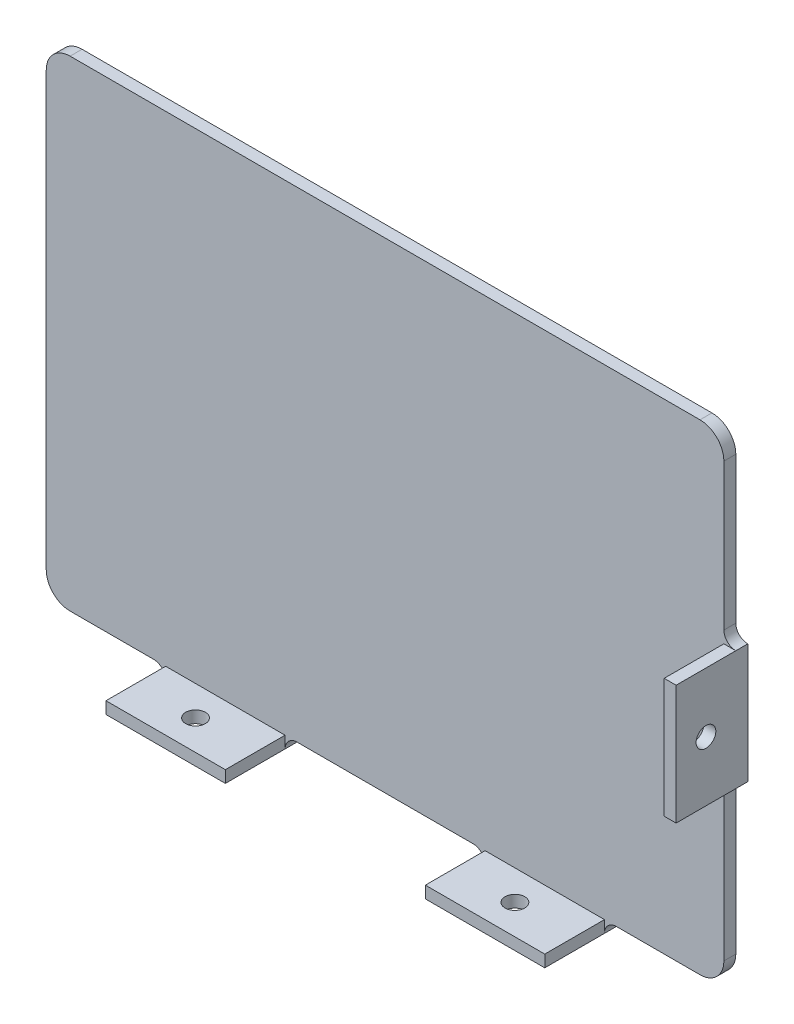
SolidWorks part; units mm, degrees
ref_plane "前视基准面" through (0, 0, 0) normal (0, 0, 1) x (1, 0, 0)
ref_plane "上视基准面" through (0, 0, 0) normal (0, 1, 0) x (1, 0, 0)
ref_plane "右视基准面" through (0, 0, 0) normal (1, 0, 0) x (0, 0, -1)
sketch "草图1" plane through (0, 0, 0) normal (0, 0, 1) x (1, 0, 0)
  line L1 (4, 0) -> (109.5, 0)
  line L2 (0, 4) -> (0, 76.5)
  line L3 (4, 80.5) -> (109.5, 80.5)
  line L4 (113.5, 4) -> (113.5, 76.5)
  arc A0 (4, 0) -> (0, 4) centre (4, 4) cw
  arc A1 (109.5, 0) -> (113.5, 4) centre (109.5, 4) ccw
  arc A2 (109.5, 80.5) -> (113.5, 76.5) centre (109.5, 76.5) cw
  arc A3 (0, 76.5) -> (4, 80.5) centre (4, 76.5) cw
  point P7 (0, 0)
  point P10 (113.5, 0)
  point P15 (0, 80.5)
  dimension "D3" = 4
  dimension "D1" = 113.5
  dimension "D2" = 80.5
extrude "凸台-拉伸1" add sketch "草图1" along normal blind 2
sketch "草图2" plane through (0, 0, 2) normal (0, 0, 1) x (1, 0, 0)
  line L0 (113.5, 4) -> (113.5, 76.5) construction
  line L1 (113.5, 50) -> (115.5, 50)
  line L2 (113.5, 50) -> (113.5, 30)
  line L3 (113.5, 30) -> (115.5, 30)
  line L4 (115.5, 50) -> (115.5, 30)
  line L5 (4, 0) -> (109.5, 0) construction
  line L10 (20, 0) -> (40, 0)
  line L11 (20, 0) -> (20, -2)
  line L12 (20, -2) -> (40, -2)
  line L13 (40, 0) -> (40, -2)
  line L14 (0, 76.5) -> (0, 4) construction
  line L15 (73.5, 0) -> (93.5, 0)
  line L16 (73.5, 0) -> (73.5, -2)
  line L17 (73.5, -2) -> (93.5, -2)
  line L18 (93.5, 0) -> (93.5, -2)
  point P6 (93.5, -3.0466)
  point P22 (93.5, -1)
  dimension "D1" = 20
  dimension "D2" = 20
  dimension "D3" = 2
  dimension "D4" = 2
  dimension "D5" = 20
  dimension "D7" = 20
  dimension "D8" = 20
  dimension "D9" = 30
extrude "凸台-拉伸2" add sketch "草图2" along normal blind 10 and the other way blind 2
sketch "草图3" plane through (115.5, 0, 0) normal (1, 0, 0) x (0, 0, -1)
  line L2 (-12, 50) -> (-12, 30) construction
  line L3 (-12, 50) -> (-2, 50) construction
  circle A1 centre (-7, 40) radius 1.65
  point P5 (-7, 50)
  point P11 (-12, 40)
  dimension "D1" = 3.3
extrude "切除-拉伸1" cut sketch "草图3" against normal blind 12
sketch "草图4" plane through (0, -2, 0) normal (0, -1, 0) x (-1, 0, 0)
  line L0 (-73.5, -12) -> (-93.5, -12) construction
  line L1 (-93.5, 0) -> (-93.5, -12) construction
  line L2 (-20, 0) -> (-20, -12) construction
  circle A0 centre (-83.5, -7) radius 1.65
  circle A1 centre (-30, -7) radius 1.65
  point P4 (-82.8674, -5.5123)
  point P5 (-30, -5.5123)
  point P12 (0, 0)
  dimension "D1" = 3.3
  dimension "D2" = 3.3
  dimension "D3" = 5
  dimension "D4" = 10
  dimension "D5" = 10
extrude "切除-拉伸2" cut sketch "草图4" against normal blind 12
fillet "圆角1" radius 2 6 edges at (113.5, 50, 1) (113.5, 30, 1) (40, 0, 1) (20, 0, 1) (73.5, 0, 1) (93.5, 0, 1)
